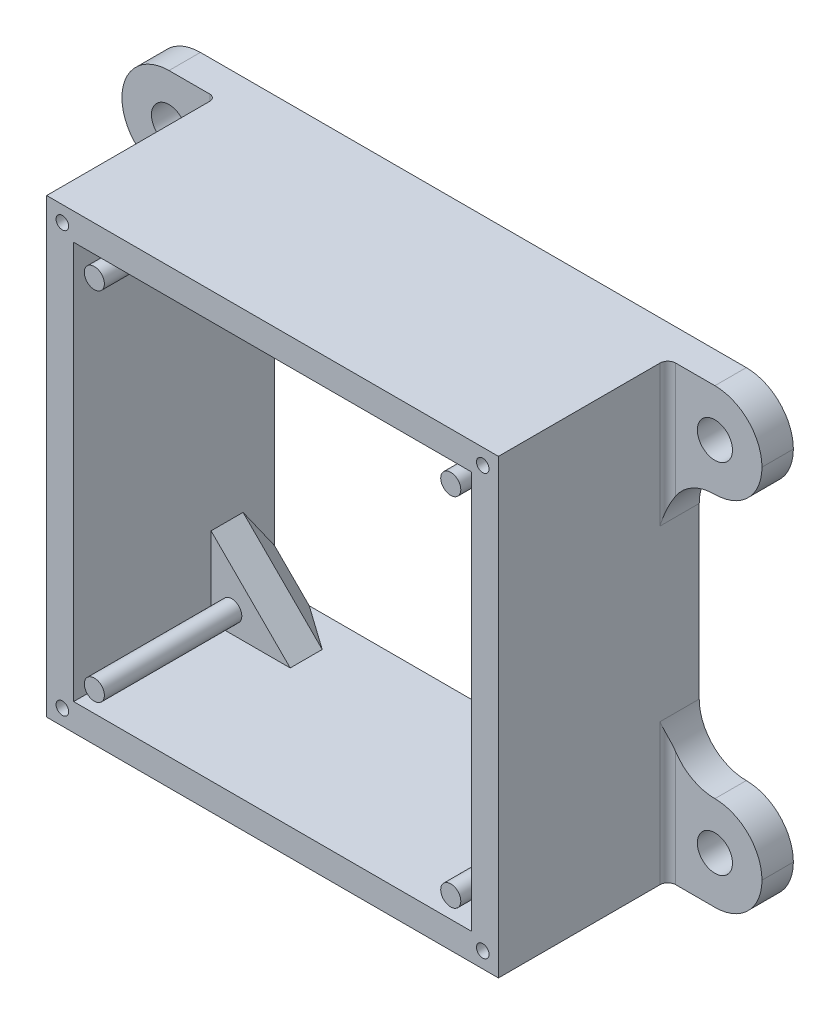
SolidWorks part; units mm, degrees
ref_plane "Front Plane" through (0, 0, 0) normal (0, 0, 1) x (1, 0, 0)
ref_plane "Top Plane" through (0, 0, 0) normal (0, 1, 0) x (1, 0, 0)
ref_plane "Right Plane" through (0, 0, 0) normal (1, 0, 0) x (0, 0, -1)
sketch "Sketch1" plane through (0, 0, 0) normal (0, 0, 1) x (1, 0, 0)
  line L1 (-40.005, -40.005) -> (40.005, -40.005)
  line L2 (-40.005, -40.005) -> (-40.005, 40.005)
  line L3 (-40.005, 40.005) -> (40.005, 40.005)
  line L4 (40.005, -40.005) -> (40.005, 40.005)
  line L5 (-40.005, -40.005) -> (40.005, 40.005) construction
  line L6 (-40.005, 40.005) -> (40.005, -40.005) construction
  point P0 (0, 0)
  dimension "D1" = 80.01
  dimension "D2" = 80.01
extrude "Boss-Extrude1" add sketch "Sketch1" along normal blind 12.827
sketch "Sketch2" plane through (0, 0, 12.827) normal (0, 0, 1) x (1, 0, 0)
  line L0 (-40.005, 0) -> (40.005, 0) construction
  line L1 (-40.005, 40.005) -> (-40.005, -40.005) construction
  line L2 (40.005, -40.005) -> (40.005, 40.005) construction
  line L3 (0, 40.005) -> (0, -40.005) construction
  line L4 (40.005, 40.005) -> (-40.005, 40.005) construction
  line L5 (-40.005, -40.005) -> (40.005, -40.005) construction
  circle A0 centre (-36.068, 36.068) radius 2.032
  circle A1 centre (36.068, 36.068) radius 2.032
  circle A2 centre (36.068, -36.068) radius 2.032
  circle A3 centre (-36.068, -36.068) radius 2.032
  dimension "D1" = 4.064
  dimension "D2" = 3.937
  dimension "D3" = 3.937
extrude "Boss-Extrude2" add sketch "Sketch2" along normal blind 27.813
sketch "Sketch3" plane through (0, 0, 0) normal (0, 0, -1) x (-1, 0, 0)
  line L4 (-40.005, -40.005) -> (-40.005, 40.005) construction
  line L5 (40.005, -40.005) -> (-40.005, -40.005) construction
  line L6 (40.005, 40.005) -> (40.005, -40.005) construction
  line L7 (-40.005, 40.005) -> (40.005, 40.005) construction
  line L8 (-45.72, 45.72) -> (-45.72, -45.72)
  line L9 (-45.72, -45.72) -> (45.72, -45.72)
  line L10 (45.72, -45.72) -> (45.72, 45.72)
  line L11 (45.72, 45.72) -> (-45.72, 45.72)
  line L12 (-45.72, 45.72) -> (-45.72, -45.72)
  line L13 (-45.72, -45.72) -> (45.72, -45.72)
  line L14 (45.72, -45.72) -> (45.72, 45.72)
  line L15 (45.72, 45.72) -> (-45.72, 45.72)
  line L16 (-40.005, -40.005) -> (-40.005, 40.005)
  line L17 (40.005, -40.005) -> (-40.005, -40.005)
  line L18 (40.005, 40.005) -> (40.005, -40.005)
  line L19 (-40.005, 40.005) -> (40.005, 40.005)
  dimension "D1" = 5.715
extrude "Boss-Extrude3" add sketch "Sketch3" against normal through all
sketch "Sketch4" plane through (0, 0, 12.827) normal (0, 0, 1) x (1, 0, 0)
  line L0 (24.13, 40.005) -> (40.005, 24.13)
  line L1 (40.005, 40.005) -> (-40.005, 40.005) construction
  line L2 (40.005, 40.005) -> (40.005, -40.005) construction
  line L3 (-24.13, 40.005) -> (-40.005, 24.13)
  line L4 (-40.005, -40.005) -> (-40.005, 40.005) construction
  line L5 (-40.005, 24.13) -> (-40.005, -24.13)
  line L6 (-40.005, 40.005) -> (-40.005, -40.005) construction
  line L7 (-40.005, -24.13) -> (-24.13, -40.005)
  line L8 (40.005, -40.005) -> (-40.005, -40.005) construction
  line L9 (-24.13, -40.005) -> (24.13, -40.005)
  line L10 (24.13, -40.005) -> (40.005, -24.13)
  line L11 (40.005, -40.005) -> (40.005, 40.005) construction
  line L12 (40.005, -24.13) -> (40.005, 24.13)
  line L13 (-24.13, 40.005) -> (24.13, 40.005)
  line L14 (-40.005, -40.005) -> (40.005, -40.005) construction
  dimension "D1" = 15.875
  dimension "D2" = 15.875
  dimension "D3" = 15.875
  dimension "D4" = 15.875
  dimension "D5" = 15.875
  dimension "D6" = 15.875
  dimension "D7" = 15.875
  dimension "D8" = 15.875
extrude "Cut-Extrude1" cut sketch "Sketch4" against normal through all
sketch "Sketch6" plane through (0, 0, 40.64) normal (0, 0, 1) x (1, 0, 0)
  line L0 (40.005, 40.005) -> (40.005, -40.005) construction
  line L1 (40.005, -40.005) -> (-40.005, -40.005) construction
  line L2 (-40.005, -40.005) -> (-40.005, 40.005) construction
  line L3 (-40.005, 40.005) -> (40.005, 40.005) construction
  line L4 (40.005, 40.005) -> (40.005, -40.005)
  line L5 (40.005, -40.005) -> (-40.005, -40.005)
  line L6 (-40.005, -40.005) -> (-40.005, 40.005)
  line L7 (-40.005, 40.005) -> (40.005, 40.005)
  line L8 (40.259, 40.259) -> (40.259, -40.259)
  line L9 (40.259, -40.259) -> (-40.259, -40.259)
  line L10 (-40.259, -40.259) -> (-40.259, 40.259)
  line L11 (-40.259, 40.259) -> (40.259, 40.259)
  dimension "D1" = 0.254
extrude "Cut-Extrude2" cut sketch "Sketch6" against normal up to surface (27.813 mm away) up to face at (-38.1, 36.068, 12.827)
sketch "Sketch7" plane through (0, 0, 12.827) normal (0, 0, 1) x (1, 0, 0)
  line L0 (-40.005, 24.13) -> (-40.005, -24.13) construction
  line L1 (-40.005, -24.13) -> (-24.13, -40.005) construction
  line L2 (-24.13, -40.005) -> (24.13, -40.005) construction
  line L3 (24.13, -40.005) -> (40.005, -24.13) construction
  line L4 (40.005, -24.13) -> (40.005, 24.13) construction
  line L5 (40.005, 24.13) -> (24.13, 40.005) construction
  line L6 (24.13, 40.005) -> (-24.13, 40.005) construction
  line L7 (-24.13, 40.005) -> (-40.005, 24.13) construction
  line L8 (-40.005, 24.13) -> (-40.005, -24.13)
  line L9 (-40.005, -24.13) -> (-24.13, -40.005)
  line L10 (-24.13, -40.005) -> (24.13, -40.005)
  line L11 (24.13, -40.005) -> (40.005, -24.13)
  line L12 (40.005, -24.13) -> (40.005, 24.13)
  line L13 (40.005, 24.13) -> (24.13, 40.005)
  line L14 (24.13, 40.005) -> (-24.13, 40.005)
  line L15 (-24.13, 40.005) -> (-40.005, 24.13)
  line L19 (-40.259, 24.2352) -> (-40.259, -24.2352)
  line L20 (-40.259, -24.2352) -> (-24.2352, -40.259)
  line L21 (-24.2352, -40.259) -> (24.2352, -40.259)
  line L22 (24.2352, -40.259) -> (40.259, -24.2352)
  line L23 (40.259, -24.2352) -> (40.259, 24.2352)
  line L24 (40.259, 24.2352) -> (24.2352, 40.259)
  line L25 (24.2352, 40.259) -> (-24.2352, 40.259)
  line L26 (-24.2352, 40.259) -> (-40.259, 24.2352)
  dimension "D1" = 0.254
extrude "Cut-Extrude3" cut sketch "Sketch7" against normal through all
sketch "Sketch9" plane through (0, 0, 0) normal (0, 0, -1) x (-1, 0, 0)
  line L0 (-45.72, 0) -> (45.72, 0) construction
  line L1 (45.72, -45.72) -> (64.77, -45.72)
  line L2 (45.72, -45.72) -> (45.72, -26.67)
  line L3 (45.72, -26.67) -> (64.77, -26.67)
  line L4 (64.77, -45.72) -> (64.77, -26.67)
  line L5 (-45.72, 45.72) -> (-45.72, -45.72) construction
  line L6 (45.72, -45.72) -> (45.72, 45.72) construction
  line L7 (64.77, 45.72) -> (64.77, 26.67)
  line L8 (45.72, 26.67) -> (64.77, 26.67)
  line L9 (45.72, 45.72) -> (64.77, 45.72)
  line L10 (45.72, 45.72) -> (45.72, 26.67)
  circle A0 centre (55.245, -36.195) radius 3.556
  circle A1 centre (55.245, 36.195) radius 3.556
  dimension "D3" = 7.112
  dimension "D1" = 19.05
  dimension "D2" = 19.05
  dimension "D4" = 9.525
  dimension "D5" = 9.525
extrude "Boss-Extrude4" add sketch "Sketch9" against normal blind 6.35
fillet "Fillet1" radius 9.525 6 edges at (-45.72, 26.67, 3.175) (-45.72, -26.67, 3.175) (-64.77, -45.72, 3.175) (-64.77, -26.67, 3.175) (-64.77, 26.67, 3.175) (-64.77, 45.72, 3.175)
fillet "Fillet2" radius 1.27 2 edges at (-45.72, -31.4325, 6.35) (-45.72, 31.4325, 6.35)
mirror "Mirror4" about plane through (0, 0, 0) normal (1, 0, 0) of "Boss-Extrude4"
fillet "Fillet3" radius 9.525 6 edges at (45.72, -26.67, 3.175) (64.77, -26.67, 3.175) (64.77, -45.72, 3.175) (45.72, 26.67, 3.175) (64.77, 26.67, 3.175) (64.77, 45.72, 3.175)
fillet "Fillet4" radius 1.5875 2 edges at (45.72, 31.4325, 6.35) (45.72, -31.4325, 6.35)
sketch "Sketch10" plane through (0, 0, 40.64) normal (0, 0, 1) x (1, 0, 0)
  line L0 (-45.72, 45.72) -> (45.72, 45.72) construction
  line L1 (-45.72, -45.72) -> (-45.72, 45.72) construction
  line L2 (45.72, 45.72) -> (45.72, -45.72) construction
  circle A0 centre (-42.545, 42.545) radius 1.27
  circle A1 centre (42.545, 42.545) radius 1.27
  circle A2 centre (42.545, -42.545) radius 1.27
  circle A3 centre (-42.545, -42.545) radius 1.27
  point P15 (0, 0)
  dimension "D1" = 2.54
  dimension "D5" = 3.175
  dimension "D2" = 3.175
  dimension "D3" = 3.175
  dimension "D6" = 3.175
  dimension "D4" = 4
extrude "Cut-Extrude4" cut sketch "Sketch10" against normal blind 7.62
chamfer "Chamfer2" distance 6.35 angle 45 4 edges at (-32.2471, -32.2471, 0) (32.2471, -32.2471, 0) (-32.2471, 32.2471, 0) (32.2471, 32.2471, 0)
